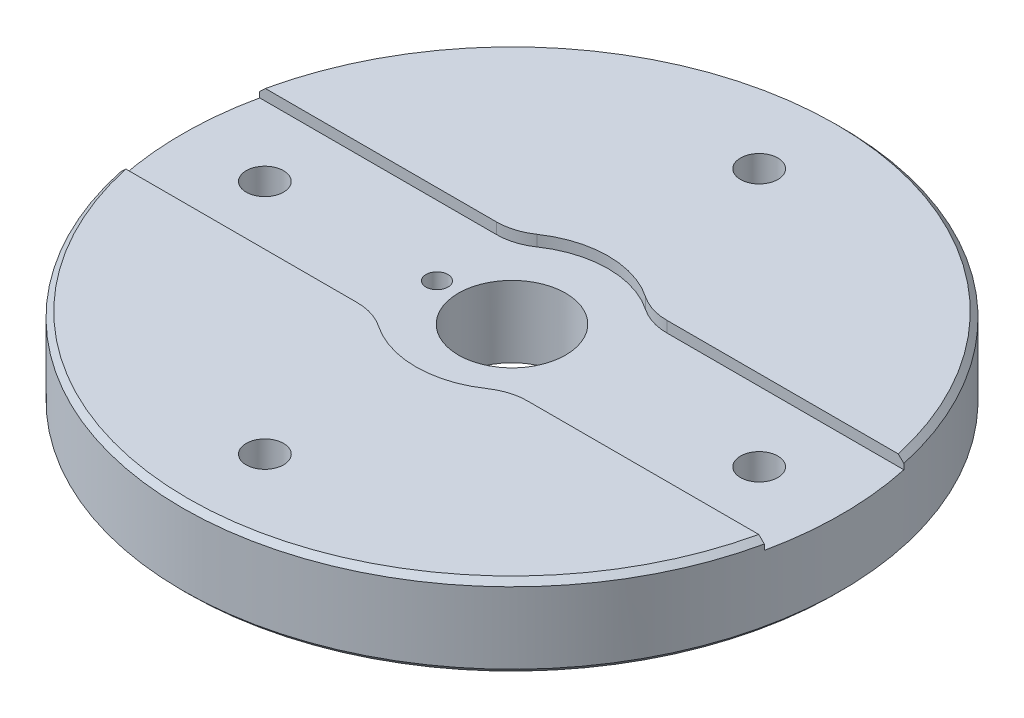
SolidWorks part; units mm, degrees
material "Plain Carbon Steel"
ref_plane "Front Plane" through (0, 0, 0) normal (0, 0, 1) x (1, 0, 0)
ref_plane "Top Plane" through (0, 0, 0) normal (0, 1, 0) x (1, 0, 0)
ref_plane "Right Plane" through (0, 0, 0) normal (1, 0, 0) x (0, 0, -1)
sketch "Sketch1" plane through (0, 0, 0) normal (0, 1, 0) x (1, 0, 0)
  circle A0 centre (0, 0) radius 60
  circle A1 centre (0, 0) radius 9.765
  dimension "D1" = 120
  dimension "D2" = 19.53
extrude "Boss-Extrude1" add sketch "Sketch1" against normal blind 15
chamfer "Chamfer1" distance 1 angle 45 2 edges at (0, -15, 60) (0, 0, 60)
hole_wizard "M8 Tapped Hole1" positions "Sketch6" profile "Sketch3" tap size "M8" standard "ISO" end condition through all
sketch "Sketch6" plane through (0, 0, 0) normal (0, 1, 0) x (1, 0, 0)
  line L0 (0, -45) -> (0, 45) construction
  line L2 (-45, 0) -> (45, 0) construction
  circle A0 centre (0, 0) radius 45
  point P10 (0, -45)
  point P11 (0, 45)
  point P14 (-45, 0)
  point P15 (45, 0)
  point P59 (0, 45)
  point P61 (45, 0)
  point P63 (0, -45)
  point P65 (-45, 0)
  dimension "D1" = 90
sketch "Sketch3" plane through (-45, 0, 0) normal (1, 0, 0) x (0, 0, 1)
  line L0 (0, 0) -> (0, 15)
  line L1 (0, 15) -> (3.4, 15)
  line L2 (3.4, 15) -> (3.4, 0)
  line L5 (3.4, 0) -> (0, 0)
  line L11 (0, -6.35) -> (0, 107.95) construction
  dimension "Thru Tap Drill Dia." = 6.8
  dimension "Thru Tap Drill Depth" = 15
cosmetic thread "Hole Thread1" parameters "D2"=8
cosmetic thread "Hole Thread2" parameters "D2"=8
cosmetic thread "Hole Thread3" parameters "D2"=8
cosmetic thread "Hole Thread4" parameters "D2"=8
sketch "Sketch5" plane through (0, -15, 0) normal (0, -1, 0) x (1, 0, 0)
  line L0 (0, 0) -> (0, 45) construction
  circle A0 centre (0, 0) radius 45 construction
  circle A1 centre (0, 45) radius 10
  dimension "D1" = 0
  dimension "D2" = 20
extrude "Cut-Extrude1" cut sketch "Sketch5" against normal blind 3 contours A1
pattern_circular "CirPattern1" count 12 every 30 about axis through (0, -15, 0) along (0, -1, 0) of "Cut-Extrude1"
sketch "Sketch7" plane through (0, 0, 0) normal (0, 1, 0) x (1, 0, 0)
  line L1 (-60, -12.7) -> (60, -12.7)
  line L2 (-60, -12.7) -> (-60, 12.7)
  line L3 (-60, 12.7) -> (60, 12.7)
  line L4 (60, -12.7) -> (60, 12.7)
  line L5 (-60, -12.7) -> (60, 12.7) construction
  line L6 (-60, 12.7) -> (60, -12.7) construction
  circle A0 centre (0, 0) radius 60 construction
  point P0 (0, 0)
  dimension "D1" = 25.4
extrude "Cut-Extrude2" cut sketch "Sketch7" against normal blind 2 contours L3 L4 L1 L2
sketch "Sketch8" plane through (0, 0, 0) normal (0, 1, 0) x (1, 0, 0)
  circle A0 centre (-13.665, 0) radius 2
  dimension "D1" = 13.665
  dimension "D2" = 4
extrude "Cut-Extrude3" cut sketch "Sketch8" against normal up to next and the other way through all
sketch "Sketch9" plane through (0, 0, 0) normal (0, 1, 0) x (1, 0, 0)
  circle A0 centre (0, 0) radius 17.5
  dimension "D1" = 35
extrude "Cut-Extrude4" cut sketch "Sketch9" against normal up to surface (2 mm away) up to face at (-13.665, -2, -2)
fillet "Fillet1" radius 10 4 edges at (-12.0399, -1, -12.7) (12.0399, -1, -12.7) (-12.0399, -1, 12.7) (12.0399, -1, 12.7)
